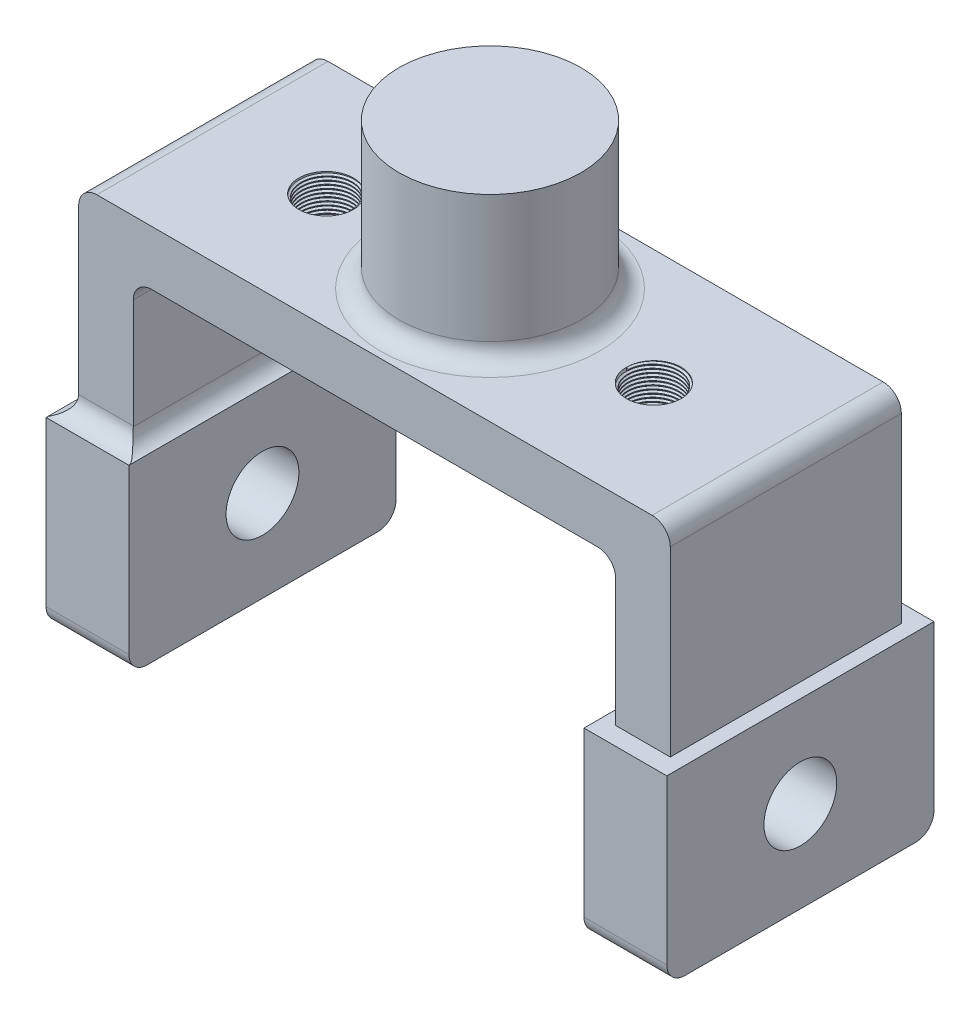
SolidWorks part; units mm, degrees
material "1060 Alloy"
ref_plane "Front Plane" through (0, 0, 0) normal (0, 0, 1) x (1, 0, 0)
ref_plane "Top Plane" through (0, 0, 0) normal (0, 1, 0) x (1, 0, 0)
ref_plane "Right Plane" through (0, 0, 0) normal (1, 0, 0) x (0, 0, -1)
sketch "Sketch2" plane through (0, 0, 0) normal (0, 1, 0) x (1, 0, 0)
  circle A0 centre (0, 0) radius 12.7
  dimension "D1" = 25.4
extrude "Boss-Extrude1" add sketch "Sketch2" along normal mid plane 20.32 contours A0
sketch "Sketch3" plane through (0, -10.16, 0) normal (0, -1, 0) x (1, 0, 0)
  line L1 (41.275, -16.1205) -> (-41.275, -16.1205)
  line L2 (41.275, -16.1205) -> (41.275, 16.1205)
  line L3 (41.275, 16.1205) -> (-41.275, 16.1205)
  line L4 (-41.275, -16.1205) -> (-41.275, 16.1205)
  line L5 (41.275, -16.1205) -> (-41.275, 16.1205) construction
  line L6 (41.275, 16.1205) -> (-41.275, -16.1205) construction
  point P0 (0, 0)
  dimension "D1" = 82.55
  dimension "D2" = 32.241
extrude "Boss-Extrude2" add sketch "Sketch3" along normal blind 7.62 contours L3 L4 L1 L2
sketch "Sketch4" plane through (0, -17.78, 0) normal (0, -1, 0) x (1, 0, 0)
  line L0 (-41.275, -16.1205) -> (-41.275, 16.1205) construction
  line L1 (-33.655, -16.1205) -> (-41.275, -16.1205)
  line L2 (-33.655, -16.1205) -> (-33.655, 16.1205)
  line L3 (-33.655, 16.1205) -> (-41.275, 16.1205)
  line L4 (-41.275, -16.1205) -> (-41.275, 16.1205)
  line L5 (-33.655, -16.1205) -> (-41.275, 16.1205) construction
  line L6 (-33.655, 16.1205) -> (-41.275, -16.1205) construction
  line L7 (41.275, 16.1205) -> (-41.275, 16.1205) construction
  line L8 (41.275, -16.1205) -> (-41.275, -16.1205) construction
  point P0 (-37.465, 0)
  dimension "D1" = 7.62
extrude "Boss-Extrude3" add sketch "Sketch4" along normal blind 20.32 contours L2 L3 L4 L1
sketch "Sketch5" plane through (0, -38.1, 0) normal (0, -1, 0) x (1, 0, 0)
  line L0 (-33.655, -16.1205) -> (-41.275, -16.1205) construction
  line L1 (-31.75, -18.6355) -> (-43.307, -18.6355)
  line L2 (-31.75, -18.6355) -> (-31.75, 18.6355)
  line L3 (-31.75, 18.6355) -> (-43.307, 18.6355)
  line L4 (-43.307, -18.6355) -> (-43.307, 18.6355)
  line L5 (-31.75, -18.6355) -> (-43.307, 18.6355) construction
  line L6 (-31.75, 18.6355) -> (-43.307, -18.6355) construction
  point P0 (-37.5285, 0)
  dimension "D1" = 37.2709
  dimension "D2" = 2.032
  dimension "D3" = 31.75
  dimension "D4" = 16.1205
extrude "Boss-Extrude4" add sketch "Sketch5" along normal blind 25.4 contours L2 L3 L4 L1
fillet "Fillet1" radius 2.54 6 edges at (-33.655, -17.78, 0) (-41.275, -10.16, 0) (-37.465, -38.1, -16.1205) (-41.275, -38.1, 0) (-33.655, -38.1, 0) (-37.465, -38.1, 16.1205)
fillet "Fillet2" radius 2.54 1 edges at (41.275, -10.16, 0)
fillet "Fillet5" radius 2.54 1 edges at (0, -10.16, 12.7)
sketch "Sketch12" plane through (-43.307, 0, 0) normal (-1, 0, 0) x (0, 0, 1)
  circle A0 centre (0, -50.8) radius 5.08
  dimension "D1" = 10.16
  dimension "D2" = 50.8
extrude "Cut-Extrude2" cut sketch "Sketch12" against normal through all contours A0
fillet "Fillet7" radius 2.54 2 edges at (-37.5285, -63.5, -18.6355) (-37.5285, -63.5, 18.6355)
mirror "Mirror1" about plane through (0, 0, 0) normal (1, 0, 0) of "Boss-Extrude3", "Boss-Extrude4", "Cut-Extrude2", "Fillet7"
sketch "Sketch13" plane through (0, -17.78, 0) normal (0, -1, 0) x (1, 0, 0)
  circle A0 centre (22.86, 0) radius 3.81
  dimension "D1" = 7.62
  dimension "D2" = 22.86
extrude "Cut-Extrude3" cut sketch "Sketch13" against normal through all and the other way through all contours A0
thread "Thread1" pitch 0.5 method extrude profile "Thread Profile1" start angle 0, offset 0, length 6.858, pitch 0.5, diameter 7.62
ref_plane "Plane1" through (19.05, -10.16, 0) normal (0, 0, 1) x (-1, 0, 0)
sketch "Thread Profile1" plane through (19.05, -10.16, 0) normal (0, 0, 1) x (-1, 0, 0)
  line L0 (0, 0) -> (0, 0.5) construction
  line L11 (0, 0) -> (0, 0.4375)
  line L12 (0, 0.4375) -> (-0.2706, 0.2812)
  line L13 (-0.2706, 0.2812) -> (-0.2706, 0.1562)
  line L15 (-0.2706, 0.1562) -> (0, 0)
  line L17 (-0.2706, 0.2187) -> (0, 0.2187) construction
  point P2 (0, 0)
  dimension "Pitch" = 0.5
  dimension "Profile_Angle" = 60
  dimension "Profile_Land" = 0.125
  dimension "Profile_Height" = 0.2706
mirror "Mirror2" about plane through (0, 0, 0) normal (1, 0, 0) of "Thread1", "Cut-Extrude3"
fillet "Fillet8" radius 2.54 1 edges at (33.655, -17.78, 0)
